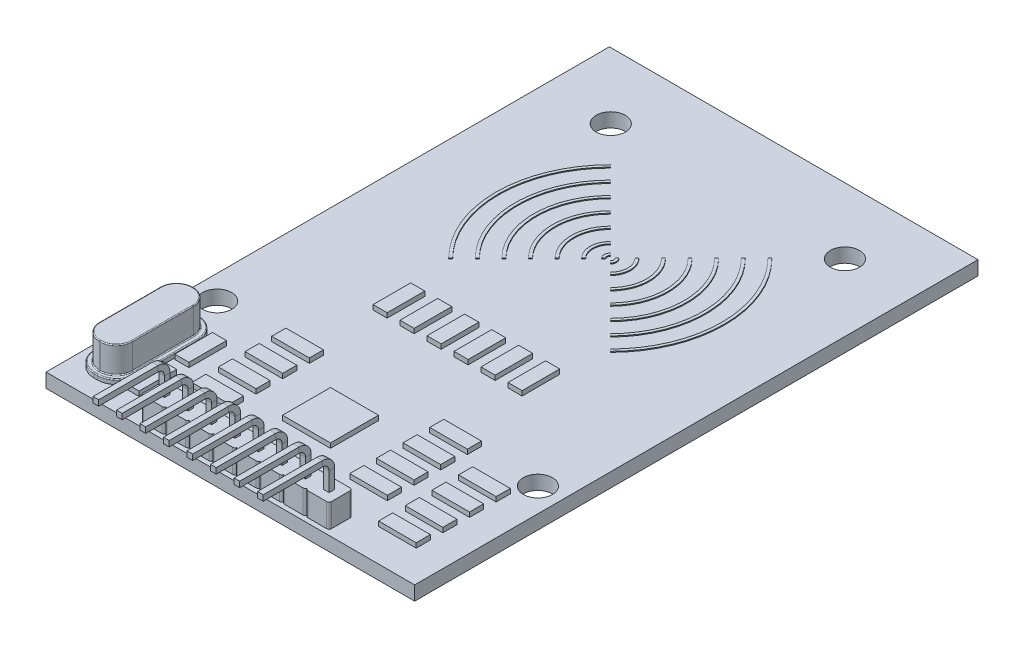
SolidWorks part; units mm, degrees
ref_plane "Front Plane" through (0, 0, 0) normal (0, 0, 1) x (1, 0, 0)
ref_plane "Top Plane" through (0, 0, 0) normal (0, 1, 0) x (1, 0, 0)
ref_plane "Right Plane" through (0, 0, 0) normal (1, 0, 0) x (0, 0, -1)
sketch "Sketch1" plane through (0, 0, 0) normal (0, 1, 0) x (1, 0, 0)
  line L1 (-19.6, 29.95) -> (19.6, 29.95)
  line L2 (-19.6, 29.95) -> (-19.6, -29.95)
  line L3 (-19.6, -29.95) -> (19.6, -29.95)
  line L4 (19.6, 29.95) -> (19.6, -29.95)
  line L5 (-19.6, 29.95) -> (19.6, -29.95) construction
  line L6 (-19.6, -29.95) -> (19.6, 29.95) construction
  point P0 (0, 0)
  dimension "D1" = 39.2
  dimension "D2" = 59.9
extrude "Boss-Extrude1" add sketch "Sketch1" along normal blind 1.5
sketch "Sketch3" plane through (0, 1.5, 0) normal (0, 1, 0) x (1, 0, 0)
  line L0 (0, 29.95) -> (0, -29.95) construction
  line L2 (19.6, 29.95) -> (-19.6, 29.95) construction
  line L3 (-17.05, -14.3) -> (17.05, -14.3) construction
  line L4 (-12.45, 22.95) -> (12.45, 22.95) construction
  line L5 (-19.6, -29.95) -> (19.6, -29.95) construction
  circle A0 centre (12.45, 22.95) radius 1.55
  circle A1 centre (-12.45, 22.95) radius 1.55
  circle A2 centre (17.05, -14.3) radius 1.55
  circle A3 centre (-17.05, -14.3) radius 1.55
  point P16 (0, 22.95)
  point P17 (0, -14.3)
  dimension "D1" = 3.1
  dimension "D2" = 12.45
  dimension "D3" = 7
  dimension "D6" = 17.05
  dimension "D7" = 15.65
extrude "Cut-Extrude1" cut sketch "Sketch3" against normal up to surface (1.5 mm away) up to face at (0, 0, 0)
sketch "Sketch4" plane through (0, 1.5, 0) normal (0, 1, 0) x (1, 0, 0)
  line L0 (-19.6, -29.95) -> (19.6, -29.95) construction
  line L1 (-9.75, -26.95) -> (-7.75, -26.95)
  line L2 (-10, -27.2) -> (-10, -29.2)
  line L3 (-9.75, -29.45) -> (-7.75, -29.45)
  line L5 (-19.6, 29.95) -> (-19.6, -29.95) construction
  line L7 (-7.25, -29.45) -> (-5.25, -29.45)
  line L9 (-7.25, -26.95) -> (-5.25, -26.95)
  line L11 (-4.75, -29.45) -> (-2.75, -29.45)
  line L13 (-4.75, -26.95) -> (-2.75, -26.95)
  line L15 (-2.25, -29.45) -> (-0.25, -29.45)
  line L17 (-2.25, -26.95) -> (-0.25, -26.95)
  line L19 (0.25, -29.45) -> (2.25, -29.45)
  line L21 (0.25, -26.95) -> (2.25, -26.95)
  line L23 (2.75, -29.45) -> (4.75, -29.45)
  line L25 (2.75, -26.95) -> (4.75, -26.95)
  line L27 (5.25, -29.45) -> (7.25, -29.45)
  line L29 (5.25, -26.95) -> (7.25, -26.95)
  line L30 (10, -27.2) -> (10, -29.2)
  line L31 (7.75, -29.45) -> (9.75, -29.45)
  line L33 (7.75, -26.95) -> (9.75, -26.95)
  line L34 (-7.5, -27.2) -> (-7.5, -29.2) [skipped]
  line L35 (-5, -27.2) -> (-5, -29.2) [skipped]
  line L36 (-2.5, -27.2) -> (-2.5, -29.2) [skipped]
  line L37 (0, -27.2) -> (0, -29.2) [skipped]
  line L38 (2.5, -27.2) -> (2.5, -29.2) [skipped]
  line L39 (5, -27.2) -> (5, -29.2) [skipped]
  line L40 (7.5, -27.2) -> (7.5, -29.2) [skipped]
  arc A1 (-7.75, -26.95) -> (-7.5, -27.2) centre (-7.75, -27.2) cw
  arc A2 (-7.5, -29.2) -> (-7.75, -29.45) centre (-7.75, -29.2) cw
  arc A3 (-9.75, -29.45) -> (-10, -29.2) centre (-9.75, -29.2) cw
  arc A4 (-10, -27.2) -> (-9.75, -26.95) centre (-9.75, -27.2) cw
  arc A5 (-5, -29.2) -> (-5.25, -29.45) centre (-5.25, -29.2) cw
  arc A6 (-7.25, -29.45) -> (-7.5, -29.2) centre (-7.25, -29.2) cw
  arc A7 (-7.5, -27.2) -> (-7.25, -26.95) centre (-7.25, -27.2) cw
  arc A8 (-5.25, -26.95) -> (-5, -27.2) centre (-5.25, -27.2) cw
  arc A10 (-2.5, -29.2) -> (-2.75, -29.45) centre (-2.75, -29.2) cw
  arc A11 (-4.75, -29.45) -> (-5, -29.2) centre (-4.75, -29.2) cw
  arc A12 (-5, -27.2) -> (-4.75, -26.95) centre (-4.75, -27.2) cw
  arc A13 (-2.75, -26.95) -> (-2.5, -27.2) centre (-2.75, -27.2) cw
  arc A15 (0, -29.2) -> (-0.25, -29.45) centre (-0.25, -29.2) cw
  arc A16 (-2.25, -29.45) -> (-2.5, -29.2) centre (-2.25, -29.2) cw
  arc A17 (-2.5, -27.2) -> (-2.25, -26.95) centre (-2.25, -27.2) cw
  arc A18 (-0.25, -26.95) -> (0, -27.2) centre (-0.25, -27.2) cw
  arc A20 (2.5, -29.2) -> (2.25, -29.45) centre (2.25, -29.2) cw
  arc A21 (0.25, -29.45) -> (0, -29.2) centre (0.25, -29.2) cw
  arc A22 (0, -27.2) -> (0.25, -26.95) centre (0.25, -27.2) cw
  arc A23 (2.25, -26.95) -> (2.5, -27.2) centre (2.25, -27.2) cw
  arc A25 (5, -29.2) -> (4.75, -29.45) centre (4.75, -29.2) cw
  arc A26 (2.75, -29.45) -> (2.5, -29.2) centre (2.75, -29.2) cw
  arc A27 (2.5, -27.2) -> (2.75, -26.95) centre (2.75, -27.2) cw
  arc A28 (4.75, -26.95) -> (5, -27.2) centre (4.75, -27.2) cw
  arc A30 (7.5, -29.2) -> (7.25, -29.45) centre (7.25, -29.2) cw
  arc A31 (5.25, -29.45) -> (5, -29.2) centre (5.25, -29.2) cw
  arc A32 (5, -27.2) -> (5.25, -26.95) centre (5.25, -27.2) cw
  arc A33 (7.25, -26.95) -> (7.5, -27.2) centre (7.25, -27.2) cw
  arc A35 (10, -29.2) -> (9.75, -29.45) centre (9.75, -29.2) cw
  arc A36 (7.75, -29.45) -> (7.5, -29.2) centre (7.75, -29.2) cw
  arc A37 (7.5, -27.2) -> (7.75, -26.95) centre (7.75, -27.2) cw
  arc A38 (9.75, -26.95) -> (10, -27.2) centre (9.75, -27.2) cw
  point P12 (-7.5, -26.95)
  point P17 (-10, -29.45)
  point P20 (-10, -26.95)
  dimension "D7" = 0.25
  dimension "D1" = 2.5
  dimension "D2" = 2.5
  dimension "D3" = 0.5
  dimension "D4" = 9.6
  dimension "D8" = 8
extrude "Boss-Extrude3" add sketch "Sketch4" along normal blind 2.5
sketch "Sketch5" plane through (0, 4, 0) normal (0, 1, 0) x (1, 0, 0)
  line L2 (-7.75, -26.95) -> (-9.75, -26.95) construction
  line L3 (-9.05, -27.9) -> (-8.45, -27.9)
  line L4 (-9.05, -27.9) -> (-9.05, -28.5)
  line L5 (-9.05, -28.5) -> (-8.45, -28.5)
  line L6 (-8.45, -27.9) -> (-8.45, -28.5)
  line L7 (-10, -27.2) -> (-10, -29.2) construction
  line L8 (-6.55, -27.9) -> (-5.95, -27.9)
  line L9 (-5.95, -27.9) -> (-5.95, -28.5)
  line L10 (-6.55, -28.5) -> (-5.95, -28.5)
  line L11 (-6.55, -27.9) -> (-6.55, -28.5)
  line L12 (-4.05, -27.9) -> (-3.45, -27.9)
  line L13 (-3.45, -27.9) -> (-3.45, -28.5)
  line L14 (-4.05, -28.5) -> (-3.45, -28.5)
  line L15 (-4.05, -27.9) -> (-4.05, -28.5)
  line L16 (-1.55, -27.9) -> (-0.95, -27.9)
  line L17 (-0.95, -27.9) -> (-0.95, -28.5)
  line L18 (-1.55, -28.5) -> (-0.95, -28.5)
  line L19 (-1.55, -27.9) -> (-1.55, -28.5)
  line L20 (0.95, -27.9) -> (1.55, -27.9)
  line L21 (1.55, -27.9) -> (1.55, -28.5)
  line L22 (0.95, -28.5) -> (1.55, -28.5)
  line L23 (0.95, -27.9) -> (0.95, -28.5)
  line L24 (3.45, -27.9) -> (4.05, -27.9)
  line L25 (4.05, -27.9) -> (4.05, -28.5)
  line L26 (3.45, -28.5) -> (4.05, -28.5)
  line L27 (3.45, -27.9) -> (3.45, -28.5)
  line L28 (5.95, -27.9) -> (6.55, -27.9)
  line L29 (6.55, -27.9) -> (6.55, -28.5)
  line L30 (5.95, -28.5) -> (6.55, -28.5)
  line L31 (5.95, -27.9) -> (5.95, -28.5)
  line L32 (8.45, -27.9) -> (9.05, -27.9)
  line L33 (9.05, -27.9) -> (9.05, -28.5)
  line L34 (8.45, -28.5) -> (9.05, -28.5)
  line L35 (8.45, -27.9) -> (8.45, -28.5)
  dimension "D1" = 0.6
  dimension "D2" = 0.6
  dimension "D3" = 0.95
  dimension "D4" = 0.95
  dimension "D5" = 8
extrude "Cut-Extrude2" cut sketch "Sketch5" against normal up to surface (4 mm away) up to face at (-17.05, 0, 15.85)
ref_plane "Plane1" through (0, -1, 0) normal (0, -1, 0) x (-1, 0, 0)
sketch "Sketch6" plane through (0, -1, 0) normal (0, -1, 0) x (-1, 0, 0)
  line L0 (6.55, -28.5) -> (5.95, -28.5)
  line L1 (9.05, -28.5) -> (8.45, -28.5)
  line L2 (9.05, -28.5) -> (9.05, -27.9)
  line L3 (9.05, -27.9) -> (8.45, -27.9)
  line L4 (8.45, -28.5) -> (8.45, -27.9)
  line L5 (5.95, -28.5) -> (5.95, -27.9)
  line L6 (6.55, -27.9) -> (5.95, -27.9)
  line L7 (6.55, -28.5) -> (6.55, -27.9)
  line L8 (4.05, -28.5) -> (3.45, -28.5)
  line L9 (3.45, -28.5) -> (3.45, -27.9)
  line L10 (4.05, -27.9) -> (3.45, -27.9)
  line L11 (4.05, -28.5) -> (4.05, -27.9)
  line L12 (1.55, -28.5) -> (0.95, -28.5)
  line L13 (0.95, -28.5) -> (0.95, -27.9)
  line L14 (1.55, -27.9) -> (0.95, -27.9)
  line L15 (1.55, -28.5) -> (1.55, -27.9)
  line L16 (-0.95, -28.5) -> (-1.55, -28.5)
  line L17 (-1.55, -28.5) -> (-1.55, -27.9)
  line L18 (-0.95, -27.9) -> (-1.55, -27.9)
  line L19 (-0.95, -28.5) -> (-0.95, -27.9)
  line L20 (-3.45, -28.5) -> (-4.05, -28.5)
  line L21 (-4.05, -28.5) -> (-4.05, -27.9)
  line L22 (-3.45, -27.9) -> (-4.05, -27.9)
  line L23 (-3.45, -28.5) -> (-3.45, -27.9)
  line L24 (-5.95, -28.5) -> (-6.55, -28.5)
  line L25 (-6.55, -28.5) -> (-6.55, -27.9)
  line L26 (-5.95, -27.9) -> (-6.55, -27.9)
  line L27 (-5.95, -28.5) -> (-5.95, -27.9)
  line L28 (-8.45, -28.5) -> (-9.05, -28.5)
  line L29 (-9.05, -28.5) -> (-9.05, -27.9)
  line L30 (-8.45, -27.9) -> (-9.05, -27.9)
  line L31 (-8.45, -28.5) -> (-8.45, -27.9)
  dimension "D1" = 8
sketch "Sketch7" plane through (-10, 0, 0) normal (-1, 0, 0) x (0, 0, 1)
  line L0 (28.2, -1) -> (28.2, 6)
  line L1 (28.5, -1) -> (27.9, -1) construction
  line L2 (29.2, 7) -> (35.5, 7)
  arc A0 (29.2, 7) -> (28.2, 6) centre (29.2, 6) ccw
  point P7 (28.2, 7)
  dimension "D3" = 1
  dimension "D1" = 7.3
  dimension "D2" = 8
sweep "Sweep1" add profiles "Sketch6" path "Sketch7"
sketch "Sketch8" plane through (0, 1.5, 0) normal (0, 1, 0) x (1, 0, 0)
  line L0 (-19.6, -29.95) -> (19.6, -29.95) construction
  line L1 (-16.5, -17.15) -> (-16.15, -17.15)
  line L2 (-18.6, -19.25) -> (-18.6, -25.85)
  line L3 (-16.5, -27.95) -> (-16.15, -27.95)
  line L4 (-14.05, -19.25) -> (-14.05, -25.85)
  line L6 (-19.6, 29.95) -> (-19.6, -29.95) construction
  arc A0 (-18.6, -25.85) -> (-16.5, -27.95) centre (-16.5, -25.85) ccw
  arc A1 (-16.15, -27.95) -> (-14.05, -25.85) centre (-16.15, -25.85) ccw
  arc A2 (-16.15, -17.15) -> (-14.05, -19.25) centre (-16.15, -19.25) cw
  arc A3 (-16.5, -17.15) -> (-18.6, -19.25) centre (-16.5, -19.25) ccw
  point P6 (-18.6, -27.95)
  point P11 (-14.05, -17.15)
  point P14 (-18.6, -17.15)
  dimension "D3" = 2.1
  dimension "D1" = 10.8
  dimension "D2" = 4.55
  dimension "D4" = 1
  dimension "D5" = 2
extrude "Boss-Extrude4" add sketch "Sketch8" along normal blind 0.5
sketch "Sketch10" plane through (0, 2, 0) normal (0, 1, 0) x (1, 0, 0)
  line L0 (-16.325, -17.15) -> (-16.325, -27.95) construction
  line L1 (-16.15, -17.15) -> (-16.5, -17.15) construction
  line L2 (-16.5, -27.95) -> (-16.15, -27.95) construction
  line L3 (-18.6, -22.55) -> (-14.05, -22.55) construction
  line L4 (-18.6, -19.25) -> (-18.6, -25.85) construction
  line L5 (-14.05, -25.85) -> (-14.05, -19.25) construction
  line L7 (-16.375, -17.6) -> (-16.275, -17.6)
  line L8 (-18.075, -19.3) -> (-18.075, -25.8)
  line L9 (-16.375, -27.5) -> (-16.275, -27.5)
  line L10 (-14.575, -19.3) -> (-14.575, -25.8)
  line L11 (-18.075, -17.6) -> (-14.575, -27.5) construction
  line L12 (-18.075, -27.5) -> (-14.575, -17.6) construction
  arc A0 (-18.075, -25.8) -> (-16.375, -27.5) centre (-16.375, -25.8) ccw
  arc A1 (-16.275, -27.5) -> (-14.575, -25.8) centre (-16.275, -25.8) ccw
  arc A2 (-14.575, -19.3) -> (-16.275, -17.6) centre (-16.275, -19.3) ccw
  arc A3 (-16.375, -17.6) -> (-18.075, -19.3) centre (-16.375, -19.3) ccw
  point P12 (-16.325, -22.55)
  dimension "D3" = 1.7
  dimension "D1" = 3.5
  dimension "D2" = 9.9
extrude "Boss-Extrude5" add sketch "Sketch10" along normal blind 2.8
fillet "Fillet1" radius 0.1 24 edges at (-17.5771, 4.8, 18.0979) (-16.325, 4.8, 17.6) (-15.0729, 4.8, 18.0979) (-14.575, 4.8, 22.55) (-15.0729, 4.8, 27.0021) (-16.325, 4.8, 27.5) (-17.5771, 4.8, 27.0021) (-17.5771, 2, 18.0979) (-16.325, 2, 17.6) (-15.0729, 2, 18.0979) (-14.575, 2, 22.55) (-15.0729, 2, 27.0021) (-16.325, 2, 27.5) (-17.5771, 2, 27.0021) (-17.9849, 2, 17.7651) (-16.325, 2, 17.15) (-14.6651, 2, 17.7651) (-14.05, 2, 22.55) (-14.6651, 2, 27.3349) (-16.325, 2, 27.95) (-17.9849, 2, 27.3349) (-18.075, 4.8, 22.55) (-18.075, 2, 22.55) (-18.6, 2, 22.55)
sketch "Sketch11" plane through (0, 1.5, 0) normal (0, 1, 0) x (1, 0, 0)
  line L0 (-0.2475, 10.6975) -> (-0.4596, 10.9096)
  line L1 (-0.35, 10.45) -> (-19.6, 10.45) construction
  line L2 (-19.6, 29.95) -> (-19.6, -29.95) construction
  line L3 (19.6, 29.95) -> (-19.6, 29.95) construction
  line L4 (0.2475, 10.6975) -> (0.4596, 10.9096)
  line L5 (-0.2475, 10.2025) -> (-0.4596, 9.9904)
  line L6 (0.2475, 10.2025) -> (0.4596, 9.9904)
  line L7 (-8.4853, 18.9353) -> (-8.5913, 19.0413)
  line L8 (-8.5913, 1.8587) -> (-8.4853, 1.9647)
  line L9 (8.4853, 1.9647) -> (8.5913, 1.8587)
  line L10 (8.4853, 18.9353) -> (8.5913, 19.0413)
  line L11 (-8.3792, 18.8292) -> (-8.4853, 18.9353)
  line L12 (-6.965, 17.415) -> (-7.1771, 17.6271)
  line L13 (-5.5508, 16.0008) -> (-5.7629, 16.2129)
  line L14 (-4.1366, 14.5866) -> (-4.3487, 14.7987)
  line L15 (-2.7224, 13.1724) -> (-2.9345, 13.3845)
  line L16 (-1.3081, 11.7581) -> (-1.5203, 11.9703)
  line L17 (-1.3081, 9.1419) -> (-1.5203, 8.9297)
  line L18 (-2.7224, 7.7276) -> (-2.9345, 7.5155)
  line L19 (-4.1366, 6.3134) -> (-4.3487, 6.1013)
  line L20 (-5.5508, 4.8992) -> (-5.7629, 4.6871)
  line L21 (-8.3792, 2.0708) -> (-8.4853, 1.9647)
  line L22 (1.3081, 9.1419) -> (1.5203, 8.9297)
  line L23 (2.7224, 7.7276) -> (2.9345, 7.5155)
  line L24 (4.1366, 6.3134) -> (4.3487, 6.1013)
  line L25 (5.5508, 4.8992) -> (5.7629, 4.6871)
  line L26 (6.965, 3.485) -> (7.1771, 3.2729)
  line L27 (8.3792, 2.0708) -> (8.4853, 1.9647)
  line L28 (1.3081, 11.7581) -> (1.5203, 11.9703)
  line L29 (2.7224, 13.1724) -> (2.9345, 13.3845)
  line L30 (4.1366, 14.5866) -> (4.3487, 14.7987)
  line L31 (5.5508, 16.0008) -> (5.7629, 16.2129)
  line L32 (6.965, 17.415) -> (7.1771, 17.6271)
  line L33 (8.3792, 18.8292) -> (8.4853, 18.9353)
  line L34 (-6.965, 3.485) -> (-7.1771, 3.2729)
  line L35 (0, 10.45) -> (0, 29.95) construction
  arc A0 (-0.3536, 10.8036) -> (-0.3536, 10.0964) centre (0, 10.45) ccw construction
  arc A1 (-1.4142, 11.8642) -> (-1.4142, 9.0358) centre (0, 10.45) ccw construction
  arc A2 (-2.8284, 13.2784) -> (-2.8284, 7.6216) centre (0, 10.45) ccw construction
  arc A3 (-4.2426, 14.6926) -> (-4.2426, 6.2074) centre (0, 10.45) ccw construction
  arc A4 (-5.6569, 16.1069) -> (-5.6569, 4.7931) centre (0, 10.45) ccw construction
  arc A5 (-5.6569, 16.1069) -> (-5.6569, 4.7931) centre (0, 10.45) ccw
  arc A6 (-7.0711, 17.5211) -> (-7.0711, 3.3789) centre (0, 10.45) ccw construction
  arc A7 (-8.4853, 18.9353) -> (-8.4853, 1.9647) centre (0, 10.45) ccw construction
  arc A8 (0.3536, 10.0964) -> (0.3536, 10.8036) centre (0, 10.45) ccw construction
  arc A9 (1.4142, 9.0358) -> (1.4142, 11.8642) centre (0, 10.45) ccw construction
  arc A10 (2.8284, 7.6216) -> (2.8284, 13.2784) centre (0, 10.45) ccw construction
  arc A11 (4.2426, 6.2074) -> (4.2426, 14.6926) centre (0, 10.45) ccw construction
  arc A12 (5.6569, 4.7931) -> (5.6569, 16.1069) centre (0, 10.45) ccw construction
  arc A13 (5.6569, 4.7931) -> (5.6569, 16.1069) centre (0, 10.45) ccw
  arc A14 (7.0711, 3.3789) -> (7.0711, 17.5211) centre (0, 10.45) ccw construction
  arc A15 (8.4853, 1.9647) -> (8.4853, 18.9353) centre (0, 10.45) ccw construction
  arc A16 (-8.5913, 19.0413) -> (-8.5913, 1.8587) centre (0, 10.45) ccw
  arc A17 (-7.1771, 17.6271) -> (-7.1771, 3.2729) centre (0, 10.45) ccw
  arc A18 (-5.7629, 16.2129) -> (-5.7629, 4.6871) centre (0, 10.45) ccw
  arc A19 (-4.3487, 14.7987) -> (-4.3487, 6.1013) centre (0, 10.45) ccw
  arc A20 (-2.9345, 13.3845) -> (-2.9345, 7.5155) centre (0, 10.45) ccw
  arc A21 (-1.5203, 11.9703) -> (-1.5203, 8.9297) centre (0, 10.45) ccw
  arc A22 (-0.4596, 10.9096) -> (-0.4596, 9.9904) centre (0, 10.45) ccw
  arc A23 (0.4596, 9.9904) -> (0.4596, 10.9096) centre (0, 10.45) ccw
  arc A24 (1.5203, 8.9297) -> (1.5203, 11.9703) centre (0, 10.45) ccw
  arc A25 (2.9345, 7.5155) -> (2.9345, 13.3845) centre (0, 10.45) ccw
  arc A26 (4.3487, 6.1013) -> (4.3487, 14.7987) centre (0, 10.45) ccw
  arc A27 (5.7629, 4.6871) -> (5.7629, 16.2129) centre (0, 10.45) ccw
  arc A28 (7.1771, 3.2729) -> (7.1771, 17.6271) centre (0, 10.45) ccw
  arc A29 (8.5913, 1.8587) -> (8.5913, 19.0413) centre (0, 10.45) ccw
  arc A30 (-8.3792, 18.8292) -> (-8.3792, 2.0708) centre (0, 10.45) ccw
  arc A31 (-6.965, 17.415) -> (-6.965, 3.485) centre (0, 10.45) ccw
  arc A32 (-5.5508, 16.0008) -> (-5.5508, 4.8992) centre (0, 10.45) ccw
  arc A33 (-4.1366, 14.5866) -> (-4.1366, 6.3134) centre (0, 10.45) ccw
  arc A34 (-2.7224, 13.1724) -> (-2.7224, 7.7276) centre (0, 10.45) ccw
  arc A35 (-1.3081, 11.7581) -> (-1.3081, 9.1419) centre (0, 10.45) ccw
  arc A36 (-0.2475, 10.6975) -> (-0.2475, 10.2025) centre (0, 10.45) ccw
  arc A37 (0.2475, 10.2025) -> (0.2475, 10.6975) centre (0, 10.45) ccw
  arc A38 (1.3081, 9.1419) -> (1.3081, 11.7581) centre (0, 10.45) ccw
  arc A39 (2.7224, 7.7276) -> (2.7224, 13.1724) centre (0, 10.45) ccw
  arc A40 (4.1366, 6.3134) -> (4.1366, 14.5866) centre (0, 10.45) ccw
  arc A41 (5.5508, 4.8992) -> (5.5508, 16.0008) centre (0, 10.45) ccw
  arc A42 (6.965, 3.485) -> (6.965, 17.415) centre (0, 10.45) ccw
  arc A43 (8.3792, 2.0708) -> (8.3792, 18.8292) centre (0, 10.45) ccw
  dimension "D1" = 45
  dimension "D2" = 0.5
  dimension "D3" = 2
  dimension "D4" = 6
  dimension "D5" = 10
  dimension "D6" = 19.5
  dimension "D10" = 8
  dimension "D11" = 4
  dimension "D12" = 12
  dimension "D7" = 45
  dimension "D8" = 45
  dimension "D9" = 45
  dimension "D13" = 0.15
  dimension "D14" = 0.15
extrude "Boss-Extrude6" add sketch "Sketch11" along normal blind 0.1 contours A16 L8 L21 A30 L11 L7 | A17 L34 A31 L12 | A18 L20 A32 L13 | A19 L19 A33 L14 | A20 L18 A34 L15 | A35 L17 A21 L16 | A36 L5 A22 L0 | A23 L4 A37 L6 | A24 L28 A38 L22 | A25 L29 A39 L23 | A26 L30 A40 L24 | A27 L31 A41 L25 | A28 L32 A42 L26 | A29 L10 L33 A43 L27 L9
sketch "Esboço1" plane through (0, 1.5, 0) normal (0, 1, 0) x (1, 0, 0)
  line L0 (6.425, -4.85) -> (5.055, -4.85) construction
  line L1 (6.425, -2.85) -> (7.925, -2.85)
  line L2 (6.425, -2.85) -> (6.425, -6.85)
  line L3 (6.425, -6.85) -> (7.925, -6.85)
  line L4 (7.925, -2.85) -> (7.925, -6.85)
  line L5 (3.555, -4.85) -> (2.185, -4.85) construction
  line L6 (5.055, -2.85) -> (3.555, -2.85)
  line L7 (5.055, -2.85) -> (5.055, -6.85)
  line L8 (5.055, -6.85) -> (3.555, -6.85)
  line L9 (3.555, -2.85) -> (3.555, -6.85)
  line L10 (2.185, -2.85) -> (0.685, -2.85)
  line L11 (2.185, -2.85) -> (2.185, -6.85)
  line L12 (2.185, -6.85) -> (0.685, -6.85)
  line L13 (0.685, -2.85) -> (0.685, -6.85)
  line L14 (-0.685, -2.85) -> (-2.185, -2.85)
  line L15 (-0.685, -2.85) -> (-0.685, -6.85)
  line L16 (-0.685, -6.85) -> (-2.185, -6.85)
  line L17 (-2.185, -2.85) -> (-2.185, -6.85)
  line L18 (-3.555, -2.85) -> (-5.055, -2.85)
  line L19 (-3.555, -2.85) -> (-3.555, -6.85)
  line L20 (-3.555, -6.85) -> (-5.055, -6.85)
  line L21 (-5.055, -2.85) -> (-5.055, -6.85)
  line L22 (-6.425, -2.85) -> (-7.925, -2.85)
  line L23 (-6.425, -2.85) -> (-6.425, -6.85)
  line L24 (-6.425, -6.85) -> (-7.925, -6.85)
  line L25 (-7.925, -2.85) -> (-7.925, -6.85)
  line L26 (-8.4, -22.15) -> (-8.4, -20.8167) construction
  line L27 (0.685, -4.85) -> (-0.685, -4.85) construction
  line L28 (-8.4, -19.3167) -> (-8.4, -17.9833) construction
  line L29 (-2.185, -4.85) -> (-3.555, -4.85) construction
  line L30 (-8.4, -16.4833) -> (-8.4, -15.15) construction
  line L31 (-5.055, -4.85) -> (-6.425, -4.85) construction
  line L32 (0, 0) -> (0, -18.65) construction
  line L33 (19.6, 29.95) -> (-19.6, 29.95) construction
  line L34 (8.4, -22.15) -> (8.4, -20.8167) construction
  line L35 (-10.4, -23.65) -> (-6.4, -23.65)
  line L36 (-10.4, -23.65) -> (-10.4, -22.15)
  line L37 (-10.4, -22.15) -> (-6.4, -22.15)
  line L38 (-6.4, -23.65) -> (-6.4, -22.15)
  line L39 (-10.4, -19.3167) -> (-6.4, -19.3167)
  line L40 (-10.4, -19.3167) -> (-10.4, -20.8167)
  line L41 (-10.4, -20.8167) -> (-6.4, -20.8167)
  line L42 (-6.4, -19.3167) -> (-6.4, -20.8167)
  line L43 (-10.4, -16.4833) -> (-6.4, -16.4833)
  line L44 (-10.4, -16.4833) -> (-10.4, -17.9833)
  line L45 (-10.4, -17.9833) -> (-6.4, -17.9833)
  line L46 (-6.4, -16.4833) -> (-6.4, -17.9833)
  line L47 (-10.4, -13.65) -> (-6.4, -13.65)
  line L48 (-10.4, -13.65) -> (-10.4, -15.15)
  line L49 (-10.4, -15.15) -> (-6.4, -15.15)
  line L50 (-6.4, -13.65) -> (-6.4, -15.15)
  line L51 (6.4, -13.65) -> (10.4, -13.65)
  line L52 (6.4, -13.65) -> (6.4, -15.15)
  line L53 (6.4, -15.15) -> (10.4, -15.15)
  line L54 (10.4, -13.65) -> (10.4, -15.15)
  line L55 (6.4, -16.4833) -> (10.4, -16.4833)
  line L56 (6.4, -16.4833) -> (6.4, -17.9833)
  line L57 (6.4, -17.9833) -> (10.4, -17.9833)
  line L58 (10.4, -16.4833) -> (10.4, -17.9833)
  line L59 (6.4, -19.3167) -> (10.4, -19.3167)
  line L60 (6.4, -19.3167) -> (6.4, -20.8167)
  line L61 (6.4, -20.8167) -> (10.4, -20.8167)
  line L62 (10.4, -19.3167) -> (10.4, -20.8167)
  line L63 (6.4, -22.15) -> (10.4, -22.15)
  line L64 (6.4, -22.15) -> (6.4, -23.65)
  line L65 (6.4, -23.65) -> (10.4, -23.65)
  line L66 (10.4, -22.15) -> (10.4, -23.65)
  line L67 (8.4, -19.3167) -> (8.4, -17.9833) construction
  line L68 (-8.4, -18.65) -> (8.4, -18.65) construction
  line L69 (8.4, -16.4833) -> (8.4, -15.15) construction
  line L70 (-19.6, 29.95) -> (-19.6, -29.95) construction
  line L71 (-13.15, -21.95) -> (-13.15, -23.25) construction
  line L72 (-13.9, -17.95) -> (-12.4, -17.95)
  line L73 (-13.9, -17.95) -> (-13.9, -21.95)
  line L74 (-13.9, -21.95) -> (-12.4, -21.95)
  line L75 (-12.4, -17.95) -> (-12.4, -21.95)
  line L76 (-13.9, -23.25) -> (-12.4, -23.25)
  line L77 (-13.9, -23.25) -> (-13.9, -27.25)
  line L78 (-13.9, -27.25) -> (-12.4, -27.25)
  line L79 (-12.4, -23.25) -> (-12.4, -27.25)
  line L80 (-19.6, -29.95) -> (19.6, -29.95) construction
  line L81 (14.3, -17.9833) -> (14.3, -19.3167) construction
  line L82 (12.3, -16.4833) -> (16.3, -16.4833)
  line L83 (12.3, -16.4833) -> (12.3, -17.9833)
  line L84 (12.3, -17.9833) -> (16.3, -17.9833)
  line L85 (16.3, -16.4833) -> (16.3, -17.9833)
  line L86 (12.3, -19.3167) -> (16.3, -19.3167)
  line L87 (12.3, -19.3167) -> (12.3, -20.8167)
  line L88 (12.3, -20.8167) -> (16.3, -20.8167)
  line L89 (16.3, -19.3167) -> (16.3, -20.8167)
  line L90 (12.3, -22.15) -> (16.3, -22.15)
  line L91 (12.3, -22.15) -> (12.3, -23.65)
  line L92 (12.3, -23.65) -> (16.3, -23.65)
  line L93 (16.3, -22.15) -> (16.3, -23.65)
  line L94 (12.3, -24.9833) -> (16.3, -24.9833)
  line L95 (12.3, -24.9833) -> (12.3, -26.4833)
  line L96 (12.3, -26.4833) -> (16.3, -26.4833)
  line L97 (16.3, -24.9833) -> (16.3, -26.4833)
  line L98 (14.3, -20.8167) -> (14.3, -22.15) construction
  line L99 (14.3, -23.65) -> (14.3, -24.9833) construction
  line L100 (19.6, -29.95) -> (19.6, 29.95) construction
  point P34 (0, -4.85)
  point P86 (0, -18.65)
  dimension "D1" = 1.5
  dimension "D2" = 4
  dimension "D3" = 1.37
  dimension "D4" = 32.8
  dimension "D5" = 43.6
  dimension "D6" = 10
  dimension "D7" = 9.2
  dimension "D8" = 9.3
  dimension "D9" = 7.2
  dimension "D10" = 12
  dimension "D11" = 3.3
extrude "Ressalto-extrusão1" add sketch "Esboço1" along normal blind 0.5
sketch "Esboço2" plane through (0, 1.5, 0) normal (0, 1, 0) x (1, 0, 0)
  line L0 (0, 0) -> (0, -16.75) construction
  line L1 (-2.55, -16.75) -> (2.55, -16.75)
  line L2 (-2.55, -16.75) -> (-2.55, -21.85)
  line L3 (-2.55, -21.85) -> (2.55, -21.85)
  line L4 (2.55, -16.75) -> (2.55, -21.85)
  line L5 (19.6, 29.95) -> (-19.6, 29.95) construction
  dimension "D1" = 5.1
  dimension "D2" = 46.7
extrude "Ressalto-extrusão2" add sketch "Esboço2" along normal blind 0.5
